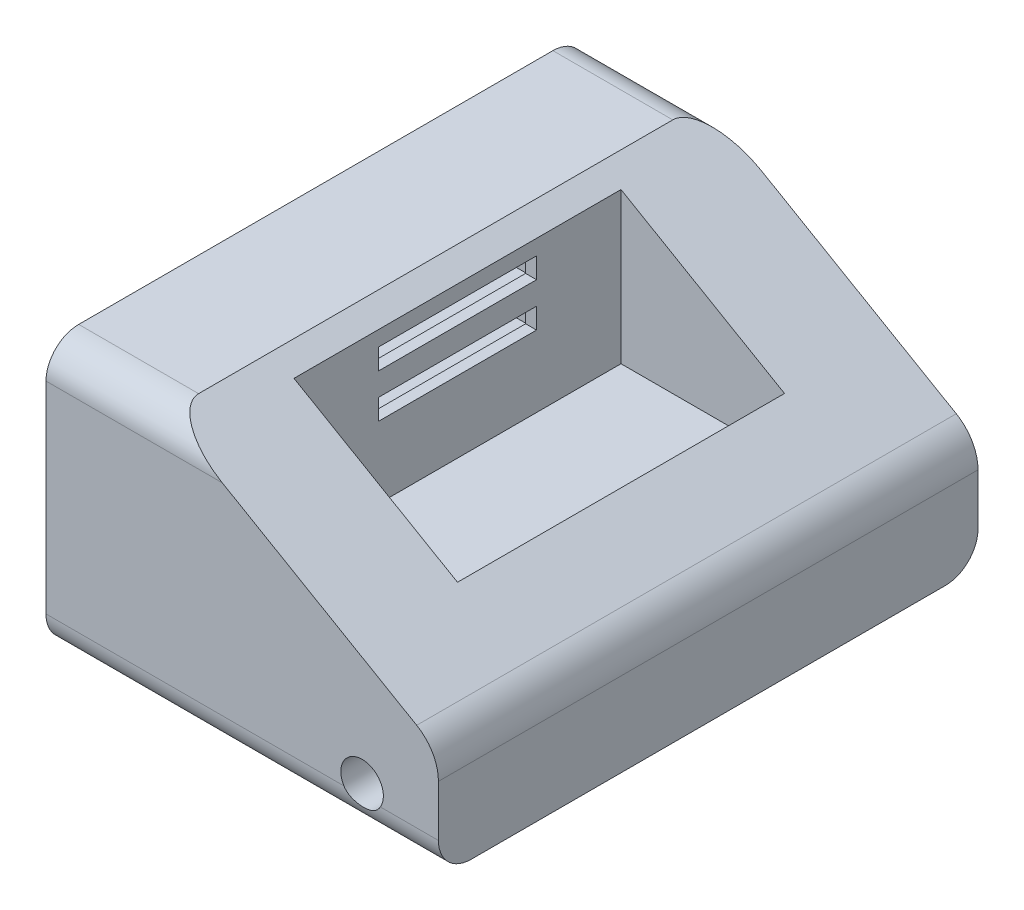
SolidWorks part; units mm, degrees
ref_plane "Спереди" through (0, 0, 0) normal (0, 0, 1) x (1, 0, 0)
ref_plane "Сверху" through (0, 0, 0) normal (0, 1, 0) x (1, 0, 0)
ref_plane "Справа" through (0, 0, 0) normal (1, 0, 0) x (0, 0, -1)
sketch "Эскиз1" plane through (0, 0, 0) normal (1, 0, 0) x (0, 0, -1)
  line L0 (-1050, 0) -> (48950, 0) construction
  line L1 (0, -1021.7777) -> (0, 48978.2223) construction
  line L2 (-24.75, -12.25) -> (24.75, -12.25)
  line L3 (-24.75, -12.25) -> (-24.75, 12.25)
  line L4 (-24.75, 12.25) -> (24.75, 12.25)
  line L5 (24.75, -12.25) -> (24.75, 12.25)
  line L6 (-24.75, -12.25) -> (24.75, 12.25) construction
  line L7 (-24.75, 12.25) -> (24.75, -12.25) construction
  point P3 (0, 0)
  dimension "D1" = 24.5
  dimension "D2" = 49.5
extrude "Бобышка-Вытянуть1" add sketch "Эскиз1" along normal blind 36
sketch "Эскиз2" plane through (0, 0, 0) normal (-1, 0, 0) x (0, 0, 1)
  line L1 (-24.75, -12.25) -> (-24.75, 12.25) construction
  line L2 (24.75, 12.25) -> (24.75, -12.25) construction
  line L3 (24.75, -12.25) -> (-24.75, -12.25) construction
  circle A0 centre (-20, -7.25) radius 2.5
  circle A1 centre (20, -7.25) radius 2.5
  dimension "D3" = 5
  dimension "D1" = 5
  dimension "D2" = 4.75
  dimension "D4" = 4.75
  dimension "D5" = 5
extrude "Вырез-Вытянуть1" cut sketch "Эскиз2" against normal blind 3
sketch "Эскиз3" plane through (0, 0, 0) normal (-1, 0, 0) x (0, 0, 1)
  line L0 (0, -1000) -> (0, 49000) construction
  line L1 (-7.6, 3.5) -> (7.6, 3.5)
  line L2 (-7.6, 7.5) -> (7.6, 7.5)
  line L3 (-7.6, 7.5) -> (-7.6, 10)
  line L4 (-7.6, 10) -> (7.6, 10)
  line L5 (7.6, 7.5) -> (7.6, 10)
  line L6 (-7.6, 7.5) -> (7.6, 10) construction
  line L7 (-7.6, 10) -> (7.6, 7.5) construction
  line L8 (-24.75, 12.25) -> (24.75, 12.25) construction
  line L9 (-7.6, 3.5) -> (-7.6, 6)
  line L10 (-7.6, 6) -> (7.6, 6)
  line L11 (7.6, 3.5) -> (7.6, 6)
  line L12 (-7.6, 3.5) -> (7.6, 6) construction
  line L13 (-7.6, 6) -> (7.6, 3.5) construction
  point P1 (0, 8.75)
  point P11 (0, 4.75)
  dimension "D1" = 15.2
  dimension "D2" = 2.5
  dimension "D3" = 2.25
  dimension "D4" = 2.5
  dimension "D5" = 4
extrude "Вырез-Вытянуть2" cut sketch "Эскиз3" against normal blind 12
fillet "Скругление1" radius 3 4 edges at (18, 12.25, -24.75) (18, -12.25, -24.75) (18, 12.25, 24.75) (18, -12.25, 24.75)
sketch "Эскиз5" plane through (0, 0, 0) normal (0, 0, 1) x (1, 0, 0)
  line L0 (36, -12.25) -> (36, -9.25) construction
  line L3 (36, -12.25) -> (0, -12.25) construction
  circle A0 centre (29, -8.25) radius 1.95
  dimension "D1" = 3.9
  dimension "D2" = 7
  dimension "D3" = 4
extrude "Вырез-Вытянуть3" cut sketch "Эскиз5" against normal through all both and the other way through all
sketch "Эскиз6" plane through (0, 0, -24.75) normal (0, 0, -1) x (-1, 0, 0)
  circle A0 centre (-29, -8.25) radius 4
  dimension "D1" = 8
extrude "Вырез-Вытянуть4" cut sketch "Эскиз6" against normal blind 3 and the other way through all
sketch "Эскиз7" plane through (0, 0, 0) normal (0, 0, 1) x (1, 0, 0)
  line L1 (24, -12.25) -> (34, -12.25)
  line L2 (24, -12.25) -> (24, -3.25)
  line L3 (24, -3.25) -> (34, -3.25)
  line L4 (34, -12.25) -> (34, -3.25)
  line L5 (24, -12.25) -> (34, -3.25) construction
  line L6 (24, -3.25) -> (34, -12.25) construction
  line L7 (36, -12.25) -> (36, -9.25) construction
  line L9 (36, -12.25) -> (0, -12.25) construction
  point P4 (29, -7.75)
  dimension "D1" = 7
  dimension "D2" = 10
  dimension "D3" = 9
extrude "Вырез-Вытянуть5" cut sketch "Эскиз7" against normal mid plane 15
sketch "Эскиз8" plane through (0, 0, -24.75) normal (0, 0, -1) x (-1, 0, 0)
  line L0 (-11, 12.25) -> (-36, -2.25)
  line L3 (-36, -2.25) -> (-36, 12.25)
  line L4 (-36, 12.25) -> (-11, 12.25)
  line L8 (-36, 12.25) -> (0, 12.25) construction
  line L9 (0, -12.25) -> (-29, -12.25) construction
  dimension "D1" = 10
  dimension "D2" = 25
extrude "Вырез-Вытянуть6" cut sketch "Эскиз8" against normal through all
fillet "Скругление2" radius 4 1 edges at (36, -2.25, 0)
sketch "Эскиз9" plane through (0, 12.25, 0) normal (0, -1, 0) x (1, 0, 0)
  line L0 (-1000, 0) -> (49000, 0) construction
  line L2 (13, -15) -> (28, -15)
  line L3 (13, -15) -> (13, 15)
  line L4 (13, 15) -> (28, 15)
  line L5 (28, -15) -> (28, 15)
  line L6 (13, -15) -> (28, 15) construction
  line L7 (13, 15) -> (28, -15) construction
  line L9 (0, 21.75) -> (0, -21.75) construction
  point P1 (20.5, 0)
  dimension "D1" = 13
  dimension "D2" = 15
  dimension "D3" = 30
extrude "Вырез-Вытянуть7" cut sketch "Эскиз9" along normal blind 15
sketch "Эскиз11" plane through (12, 0, 0) normal (-1, 0, 0) x (0, 0, 1)
  line L0 (-1007.6, 8.75) -> (48992.4, 8.75) construction
  line L1 (-7.25, 9.7) -> (7.25, 9.7)
  line L2 (-7.25, 9.7) -> (-7.25, 7.8)
  line L3 (-7.25, 7.8) -> (7.25, 7.8)
  line L4 (7.25, 9.7) -> (7.25, 7.8)
  line L5 (-7.25, 9.7) -> (7.25, 7.8) construction
  line L6 (-7.25, 7.8) -> (7.25, 9.7) construction
  line L7 (-7.6, 10) -> (-7.6, 7.5) construction
  line L8 (-1007.6, 4.75) -> (48992.4, 4.75) construction
  line L9 (-7.6, 6) -> (-7.6, 3.5) construction
  line L10 (0, -990) -> (0, 49010) construction
  line L11 (7.6, 10) -> (-7.6, 10) construction
  line L13 (-7.25, 5.7) -> (7.25, 5.7)
  line L14 (-7.25, 5.7) -> (-7.25, 3.8)
  line L15 (-7.25, 3.8) -> (7.25, 3.8)
  line L16 (7.25, 5.7) -> (7.25, 3.8)
  line L17 (-7.25, 5.7) -> (7.25, 3.8) construction
  line L18 (-7.25, 3.8) -> (7.25, 5.7) construction
  point P0 (0, 8.75)
  point P10 (-7.6, 8.75)
  point P15 (-7.6, 4.75)
  point P16 (0, 4.75)
  point P20 (0, 10)
  dimension "D1" = 1.9
  dimension "D2" = 14.5
  dimension "D3" = 1.9
extrude "Вырез-Вытянуть8" cut sketch "Эскиз11" against normal blind 2
